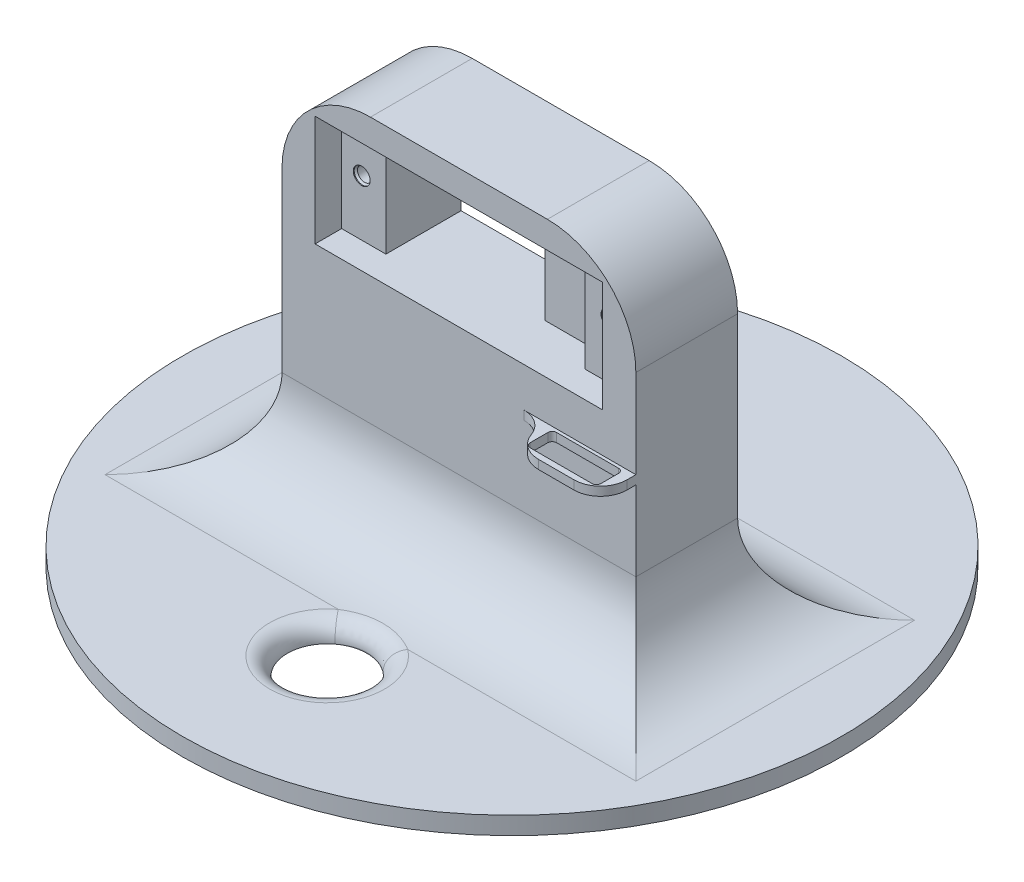
SolidWorks part; units mm, degrees
ref_plane "Front Plane" through (0, 0, 0) normal (0, 0, 1) x (1, 0, 0)
ref_plane "Top Plane" through (0, 0, 0) normal (0, 1, 0) x (1, 0, 0)
ref_plane "Right Plane" through (0, 0, 0) normal (1, 0, 0) x (0, 0, -1)
sketch "Sketch1" plane through (0, 0, 0) normal (0, 1, 0) x (1, 0, 0)
  circle A0 centre (0, 0) radius 37.25
  dimension "D1" = 74.5
extrude "Boss-Extrude1" add sketch "Sketch1" along normal blind 2
sketch "Sketch2" plane through (0, 2, 0) normal (0, 1, 0) x (1, 0, 0)
  line L1 (20, 6) -> (-20, 6)
  line L2 (20, 6) -> (20, -6)
  line L3 (20, -6) -> (-20, -6)
  line L4 (-20, 6) -> (-20, -6)
  line L5 (20, 6) -> (-20, -6) construction
  line L6 (20, -6) -> (-20, 6) construction
  point P0 (0, 0)
  dimension "D1" = 12
  dimension "D2" = 40
extrude "Boss-Extrude4" add sketch "Sketch2" along normal blind 40
sketch "Sketch3" plane through (0, 0, 6) normal (0, 0, 1) x (1, 0, 0)
  line L1 (16.2459, 38.9602) -> (-16.2541, 38.9602)
  line L2 (16.2459, 38.9602) -> (16.2459, 26.4602)
  line L3 (16.2459, 26.4602) -> (-16.2541, 26.4602)
  line L4 (-16.2541, 38.9602) -> (-16.2541, 26.4602)
  line L5 (16.2459, 38.9602) -> (-16.2541, 26.4602) construction
  line L6 (16.2459, 26.4602) -> (-16.2541, 38.9602) construction
  point P0 (-0.0041, 32.7102)
  dimension "D1" = 32.5
  dimension "D2" = 12.5
extrude "Cut-Extrude1" cut sketch "Sketch3" against normal blind 3
sketch "Sketch4" plane through (0, 0, 3) normal (0, 0, 1) x (1, 0, 0)
  line L0 (16.2459, 38.9602) -> (-16.2541, 38.9602) construction
  line L1 (-11.2541, 38.9602) -> (11.2459, 38.9602)
  line L2 (-11.2541, 38.9602) -> (-11.2541, 26.4602)
  line L3 (-11.2541, 26.4602) -> (11.2459, 26.4602)
  line L4 (11.2459, 38.9602) -> (11.2459, 26.4602)
  line L5 (-16.2541, 26.4602) -> (16.2459, 26.4602) construction
  line L6 (-16.2541, 38.9602) -> (-16.2541, 26.4602) construction
  line L7 (16.2459, 26.4602) -> (16.2459, 38.9602) construction
  dimension "D1" = 5
  dimension "D2" = 5
extrude "Cut-Extrude2" cut sketch "Sketch4" against normal blind 2.5
sketch "Sketch5" plane through (0, 0, 0.5) normal (0, 0, 1) x (1, 0, 0)
  line L0 (-16.2541, 26.4602) -> (16.2459, 26.4602) construction
  line L1 (-11.2541, 38.9602) -> (4.2459, 38.9602)
  line L2 (-11.2541, 38.9602) -> (-11.2541, 26.4602)
  line L3 (-11.2541, 26.4602) -> (4.2459, 26.4602)
  line L4 (4.2459, 38.9602) -> (4.2459, 26.4602)
  dimension "D1" = 15.5
extrude "Cut-Extrude3" cut sketch "Sketch5" against normal blind 6
sketch "Sketch6" plane through (20, 0, 0) normal (1, 0, 0) x (0, 0, -1)
  line L0 (-6, 2) -> (6, 2) construction
  line L1 (6, 42) -> (5.5, 42)
  line L2 (6, 42) -> (6, 2)
  line L3 (6, 2) -> (5.5, 2)
  line L4 (5.5, 42) -> (5.5, 2)
  dimension "D1" = 0.5
extrude "Cut-Extrude4" cut sketch "Sketch6" against normal through all
sketch "Sketch7" plane through (0, 0, 3) normal (0, 0, 1) x (1, 0, 0)
  circle A0 centre (14.0139, 32.7558) radius 0.95
  circle A1 centre (-13.9861, 32.7558) radius 0.95
  dimension "D1" = 1.9
  dimension "D2" = 1.9
  dimension "D3" = 28
extrude "Cut-Extrude5" cut sketch "Sketch7" against normal blind 0.1
hole_wizard "M2x0.4 Tapped Hole1" positions "Sketch8" profile "Sketch9" tap size "M2x0.4" standard "ANSI Metric" end condition through all
sketch "Sketch8" plane through (0, 0, 2.9) normal (0, 0, 1) x (1, 0, 0)
  point P0 (-13.9861, 32.7558)
  point P3 (14.0139, 32.7558)
sketch "Sketch9" plane through (-13.9861, 32.7558, 2.9) normal (1, 0, 0) x (0, -1, 0)
  line L0 (0, 0) -> (0, 40.15)
  line L1 (0, 40.15) -> (0.8, 40.15)
  line L2 (0.8, 40.15) -> (0.8, 0.225)
  line L3 (0.8, 0.225) -> (1.025, 0)
  line L5 (1.025, 0) -> (0, 0)
  line L6 (-0.8, 0.225) -> (-1.025, 0) construction
  line L11 (0, -6.35) -> (0, 107.95) construction
  dimension "Thru Tap Drill Dia." = 1.6
  dimension "Thru Tap Drill Depth" = 40.15
  dimension "Near C'Sink Dia." = 2.05
  dimension "Near C'Sink Angle" = 90
cosmetic thread "Hole Thread1" parameters "D2"=2
cosmetic thread "Hole Thread2" parameters "D2"=2
sketch "Sketch11" plane through (20, 0, 0) normal (1, 0, 0) x (0, 0, -1)
  line L0 (-6, 22) -> (-10, 22)
  line L1 (-6, 42) -> (-6, 2) construction
  line L2 (-10, 22) -> (-10, 21)
  line L3 (-10, 21) -> (-6, 21)
  line L4 (-6, 22) -> (-6, 21)
  point P4 (-6, 21.5)
  point P7 (-8, 21)
  dimension "D1" = 4
  dimension "D2" = 1
extrude "Boss-Extrude9" add sketch "Sketch11" against normal blind 10
sketch "Sketch13" plane through (0, 22, 0) normal (0, 1, 0) x (1, 0, 0)
  line L1 (18.8946, -6.3461) -> (10.8946, -6.3461)
  line L2 (18.8946, -6.3461) -> (18.8946, -9.3461)
  line L3 (18.8946, -9.3461) -> (10.8946, -9.3461)
  line L4 (10.8946, -6.3461) -> (10.8946, -9.3461)
  dimension "D1" = 8
  dimension "D2" = 3
extrude "Cut-Extrude6" cut sketch "Sketch13" against normal up to next
fillet "Fillet4" radius 0.5 4 edges at (18.8946, 21.5, 9.3461) (10.8946, 21.5, 9.3461) (18.8946, 21.5, 6.3461) (10.8946, 21.5, 6.3461)
fillet "Fillet5" radius 3 2 edges at (10, 21.5, 10) (20, 21.5, 10)
fillet "Fillet6" radius 3 1 edges at (10, 21.5, 6)
fillet "Fillet7" radius 10 4 edges at (-20, 2, 0.25) (20, 2, 0.25) (0, 2, -5.5) (0, 2, 6)
fillet "Fillet8" radius 10 2 edges at (20, 42, 0.25) (-20, 42, 0.25)
sketch "Sketch14" plane through (0, 2, 0) normal (0, 1, 0) x (1, 0, 0)
  circle A0 centre (0.2935, -21.1814) radius 4.5
  dimension "D1" = 9
extrude "Cut-Extrude7" cut sketch "Sketch14" against normal up to next contours A0
fillet "Fillet10" radius 2 1 edges at (0.2935, 2, 25.6814)
